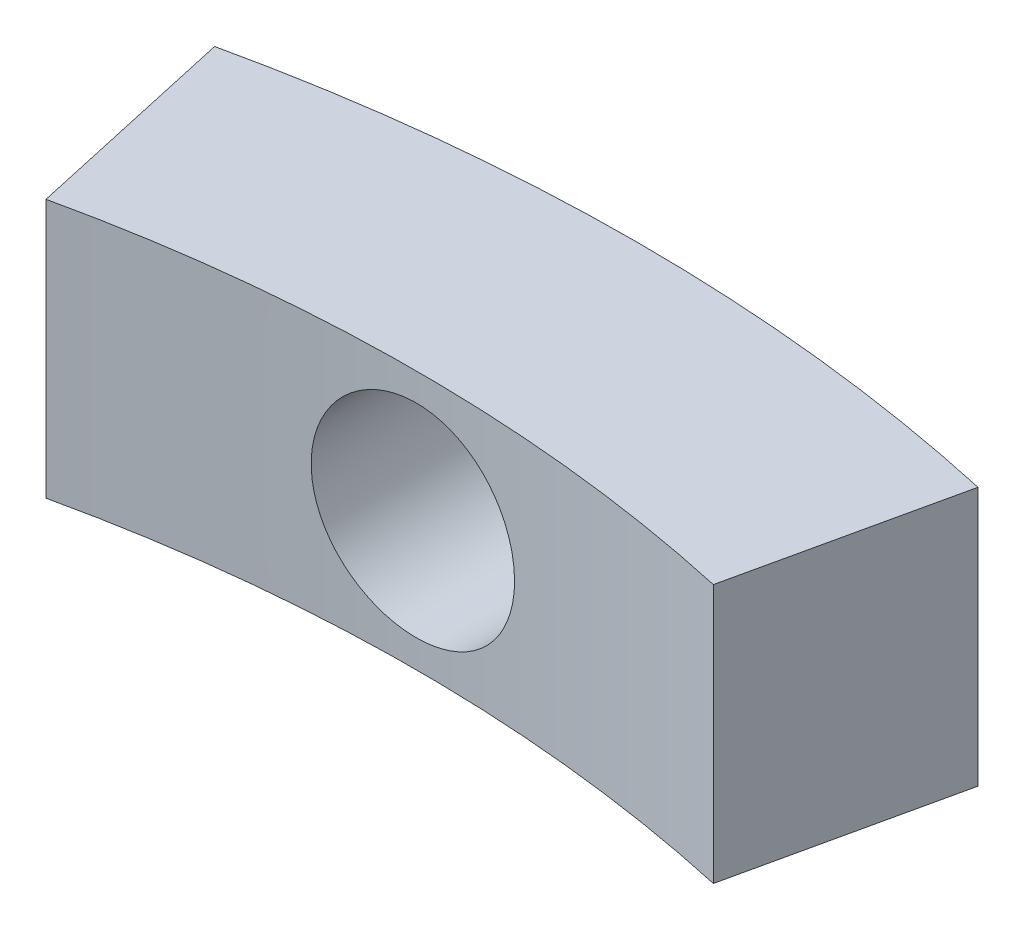
SolidWorks part; units mm, degrees
ref_plane "Front Plane" through (0, 0, 0) normal (0, 0, 1) x (1, 0, 0)
ref_plane "Top Plane" through (0, 0, 0) normal (0, 1, 0) x (1, 0, 0)
ref_plane "Right Plane" through (0, 0, 0) normal (1, 0, 0) x (0, 0, -1)
sketch "Sketch2" plane through (0, 0, 0) normal (0, 1, 0) x (1, 0, 0)
  line L0 (-10.3217, -1.1304) -> (-9.023, -6.9882)
  line L1 (9.023, -6.9882) -> (10.3217, -1.1304)
  line L2 (0, 16.9133) -> (0, -16.9133) construction
  line L3 (-2.75, -0.0794) -> (-2.75, -4.5125)
  line L4 (-2.75, -4.5125) -> (2.75, -4.5125)
  line L5 (2.75, -4.5125) -> (2.75, -0.0794)
  arc A0 (9.023, -6.9882) -> (-9.023, -6.9882) centre (0, -47.6885) ccw
  arc A1 (10.3217, -1.1304) -> (-10.3217, -1.1304) centre (0, -47.6885) ccw
  point P10 (0, 0)
  point P14 (0, -4.5125)
  point P15 (2.5267, -4.5125)
  dimension "D2" = 47.6885
  dimension "D3" = 25
  dimension "D4" = 5.5
  dimension "D5" = 0.0794
  dimension "D1" = 6
extrude "Boss-Extrude1" add sketch "Sketch2" along normal mid plane 7 contours L2 L4 L3 A1 L0 A0 | L2 A1 L3 L4 | L4 L2 A0 L1 A1 L5 | A1 L2 L4 L5 region at (-5.7959, 0, 3.559) region at (-1.3709, 0, 2.2694) region at (5.7959, 0, 3.559) region at (1.3709, 0, 2.2694)
sketch "Sketch3" plane through (0, 0, 0) normal (0, 0, 1) x (1, 0, 0)
  circle A0 centre (0, 0) radius 2.75
  dimension "D1" = 5.5
extrude "Cut-Extrude3" cut sketch "Sketch3" against normal through all and the other way through all contours A0 region at (0, 0, 0)
equation "\"Thiccness\"= 6mm"
equation "\"D1@Sketch2\"=\"Thiccness\""
equation "\"Coupler_ID\" = 3.755in"
equation "\"M4_Insert_OD\" = 5.5mm"
equation "\"Height\" = 7mm"
equation "\"D2@Sketch2\"=\"Coupler_ID\"/2"
equation "\"Angle\"= 25deg"
equation "\"D3@Sketch2\"=\"Angle\""
equation "\"D1@Boss-Extrude1\"=\"Height\""
equation "\"D4@Sketch2\"=\"M4_Insert_OD\""
equation "\"D1@Sketch3\"=\"M4_Insert_OD\""
